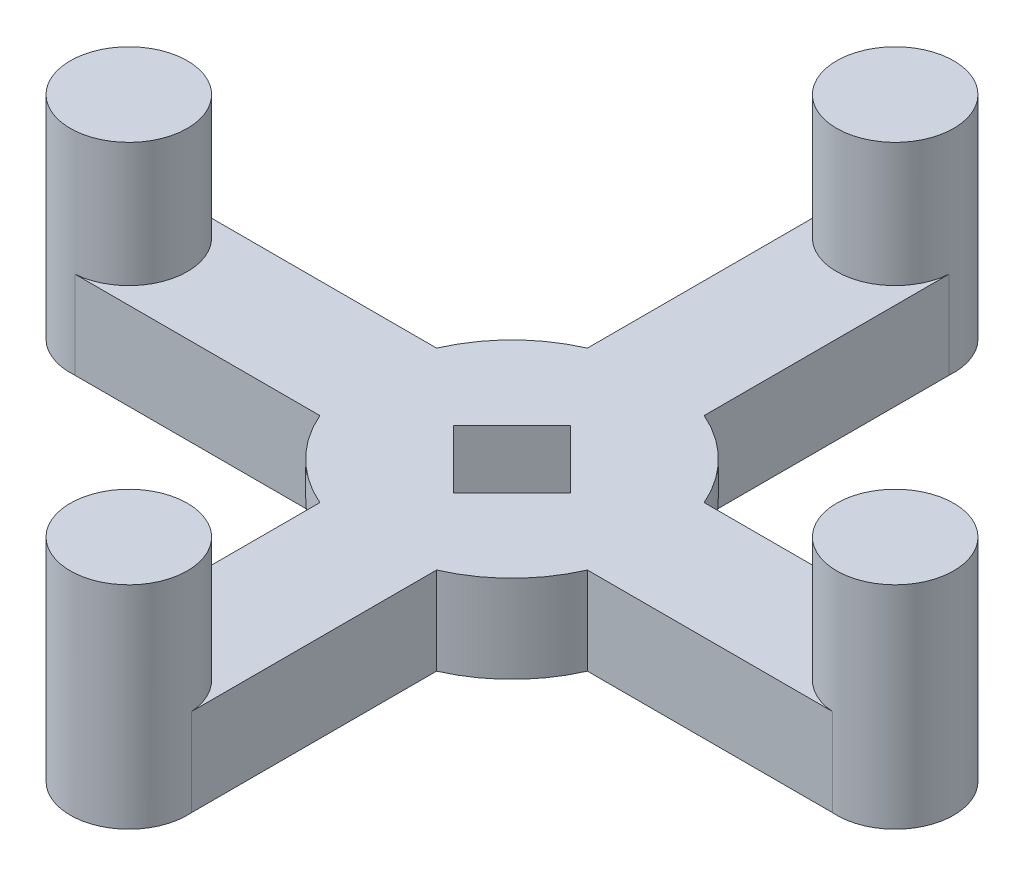
SolidWorks part; units mm, degrees
material "PLA personnalisé"
ref_plane "Plan de face" through (0, 0, 0) normal (0, 0, 1) x (1, 0, 0)
ref_plane "Plan de dessus" through (0, 0, 0) normal (0, 1, 0) x (1, 0, 0)
ref_plane "Plan de droite" through (0, 0, 0) normal (1, 0, 0) x (0, 0, -1)
sketch "Esquisse1" plane through (0, 0, 0) normal (0, 1, 0) x (1, 0, 0)
  line L0 (4, -26.25) -> (4, 26.25)
  line L1 (4, -26.25) -> (-4, -26.25)
  line L2 (4, 26.25) -> (-4, 26.25)
  line L3 (-4, -26.25) -> (-4, 26.25)
  line L4 (4, -26.25) -> (-4, 26.25) construction
  line L5 (4, 26.25) -> (-4, -26.25) construction
  line L6 (26.25, 4) -> (-26.25, 4)
  line L7 (26.25, 4) -> (26.25, -4)
  line L8 (-26.25, 4) -> (-26.25, -4)
  line L9 (26.25, -4) -> (-26.25, -4)
  line L10 (26.25, 4) -> (-26.25, -4) construction
  line L11 (-26.25, 4) -> (26.25, -4) construction
  circle A0 centre (0, 0) radius 26.25
  circle A1 centre (0, 0) radius 10
  dimension "D1" = 52.5
  dimension "D4" = 20
  dimension "D2" = 8
  dimension "D3" = 8
extrude "Boss.-Extru.1" add sketch "Esquisse1" along normal blind 3 and the other way blind 3 contours A1 L0 A0 L3 | A1 L6 A0 L9 | A1 L3 A0 L0 | A1 L9 A0 L6 | A1 region at (0, 0, 17.9357) region at (17.9357, 0, 0) region at (-17.9357, 0, 0) region at (0, 0, -17.9357)
sketch "Esquisse2" plane through (0, 3, 0) normal (0, 1, 0) x (1, 0, 0)
  circle A0 centre (0, 26.25) radius 4.0117
  arc A1 (4, 25.9434) -> (-4, 25.9434) centre (0, 0) ccw construction
extrude "Boss.-Extru.2" add sketch "Esquisse2" along normal blind 8.5 and the other way blind 6
pattern_circular "Répétition circulaire1" count 4 over 360 about axis through (0, 3, 0) along (0, 1, 0) of "Boss.-Extru.2"
ref_plane "Plan1" through (0, 0, 0) normal (0.7071, 0, -0.7071) x (-0.7071, 0, -0.7071)
sketch "Esquisse3" plane through (0, 0, 0) normal (0.7071, 0, -0.7071) x (-0.7071, 0, -0.7071)
  circle A0 centre (0, 0) radius 1.05
  dimension "D1" = 2.1
extrude "Enlèv. mat.-Extru.1" cut sketch "Esquisse3" against normal through all and the other way through all
sketch "Esquisse4" plane through (0, 0, 0) normal (0, 1, 0) x (1, 0, 0)
  line L0 (19.3622, 0) -> (-18.228, 0) construction
  line L1 (0, 0) -> (18.7951, 18.7951) construction
  line L2 (-4.0001, 0) -> (0, 4.0001)
  line L3 (-4.0001, 0) -> (0, -4.0001)
  line L4 (0, 4.0001) -> (4.0001, 0)
  line L5 (0, -4.0001) -> (4.0001, 0)
  line L6 (-4.0001, 0) -> (4.0001, 0) construction
  line L7 (0, 4.0001) -> (0, -4.0001) construction
  point P6 (2.0001, 2.0001)
  dimension "D1" = 45
  dimension "D2" = 5.657
  dimension "D3" = 5.657
extrude "Enlèv. mat.-Extru.2" cut sketch "Esquisse4" against normal through all and the other way through all
